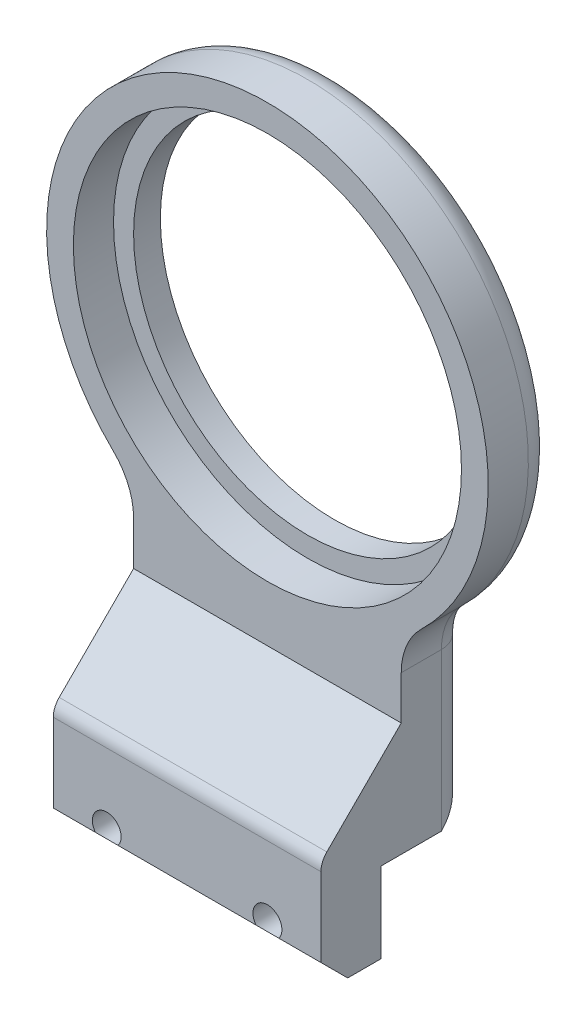
SolidWorks part; units mm, degrees
ref_plane "前视基准面" through (0, 0, 0) normal (0, 0, 1) x (1, 0, 0)
ref_plane "上视基准面" through (0, 0, 0) normal (0, 1, 0) x (1, 0, 0)
ref_plane "右视基准面" through (0, 0, 0) normal (1, 0, 0) x (0, 0, -1)
other "Configuration Table"
sketch "草图1" plane through (0, 0, 0) normal (0, 0, 1) x (1, 0, 0)
  line L0 (0, 27.158) -> (0, -27.158) construction
  line L1 (20, -27.158) -> (-20, -27.158)
  line L5 (-20, -27.158) -> (-20, 0.9092)
  line L6 (20, -27.158) -> (20, 0.9092)
  circle A1 centre (0, 27.158) radius 26
  arc A2 (20, 0.9092) -> (-20, 0.9092) centre (0, 27.158) ccw
  point P0 (0, 0)
  point P22 (0, 27.158)
extrude "凸台-拉伸1" add sketch "草图1" along normal blind 10
sketch "草图3" plane through (0, 0, 10) normal (0, 0, 1) x (1, 0, 0)
  circle A0 centre (0, 27.158) radius 29
extrude "切除-拉伸1" cut sketch "草图3" against normal blind 6
sketch "草图4" plane through (0, 0, 10) normal (0, 0, 1) x (1, 0, 0)
  line L1 (-20, -27.158) -> (20, -27.158)
  line L2 (-20, -27.158) -> (-20, -39.158)
  line L3 (-20, -39.158) -> (20, -39.158)
  line L4 (20, -27.158) -> (20, -39.158)
extrude "凸台-拉伸2" add sketch "草图4" along normal blind 12 separate body
sketch "草图5" plane through (0, 0, 10) normal (0, 0, -1) x (-1, 0, 0)
  line L1 (-20, -27.158) -> (20, -27.158)
  line L2 (-20, -27.158) -> (-20, -39.158)
  line L3 (-20, -39.158) -> (20, -39.158)
  line L4 (20, -27.158) -> (20, -39.158)
extrude "凸台-拉伸3" add sketch "草图5" along normal blind 2
sketch "草图6" plane through (0, -27.158, 0) normal (0, 1, 0) x (1, 0, 0)
  line L1 (-20, -10) -> (20, -10)
  line L2 (-20, -10) -> (-20, -22)
  line L3 (-20, -22) -> (20, -22)
  line L4 (20, -10) -> (20, -22)
extrude "凸台-拉伸4" add sketch "草图6" along normal blind 3
chamfer "倒角1" distance 14 angle 45 1 edges at (0, -24.158, 10)
sketch "草图7" plane through (0, 0, 8) normal (0, 0, -1) x (-1, 0, 0)
  line L0 (0, -27.158) -> (0, -33.8336) construction
  line L2 (0, -33.8336) -> (-12, -33.8336) construction
  line L3 (0, -33.8336) -> (12.013, -33.8336) construction
  circle A0 centre (-12, -33.8336) radius 1.7
  circle A1 centre (12.013, -33.8336) radius 1.7
extrude "切除-拉伸2" cut sketch "草图7" against normal blind 14
sketch "草图8" plane through (0, 0, 22) normal (0, 0, 1) x (1, 0, 0)
  circle A0 centre (-12.013, -33.8336) radius 2.15
  circle A1 centre (12, -33.8336) radius 2.165
extrude "切除-拉伸3" cut sketch "草图8" against normal blind 6
sketch "草图9" plane through (0, 0, 8) normal (0, 0, -1) x (-1, 0, 0)
  line L0 (-20, -39.158) -> (20, -39.158) construction
  line L1 (-20, -27.158) -> (20, -27.158)
  line L2 (-20, -27.158) -> (-20, -39.158)
  line L3 (-20, -39.158) -> (20, -39.158)
  line L4 (20, -27.158) -> (20, -39.158)
extrude "切除-拉伸4" cut sketch "草图9" against normal blind 5
chamfer "倒角2" distance 4 angle 45 1 edges at (0, -39.158, 22)
chamfer "倒角3" distance 4 angle 45 1 edges at (0, -27.158, 0)
fillet "圆角5" radius 10 2 edges at (-20, 0.9092, 5) (20, 0.9092, 5)
fillet "圆角6" radius 4 5 edges at (0, 60.158, 0) (-20, -13.4029, 0) (-20.7868, 0.2401, 0) (20.7868, 0.2401, 0) (20, -13.4029, 0)
fillet "圆角7" radius 3 1 edges at (0, -22.158, 22)
